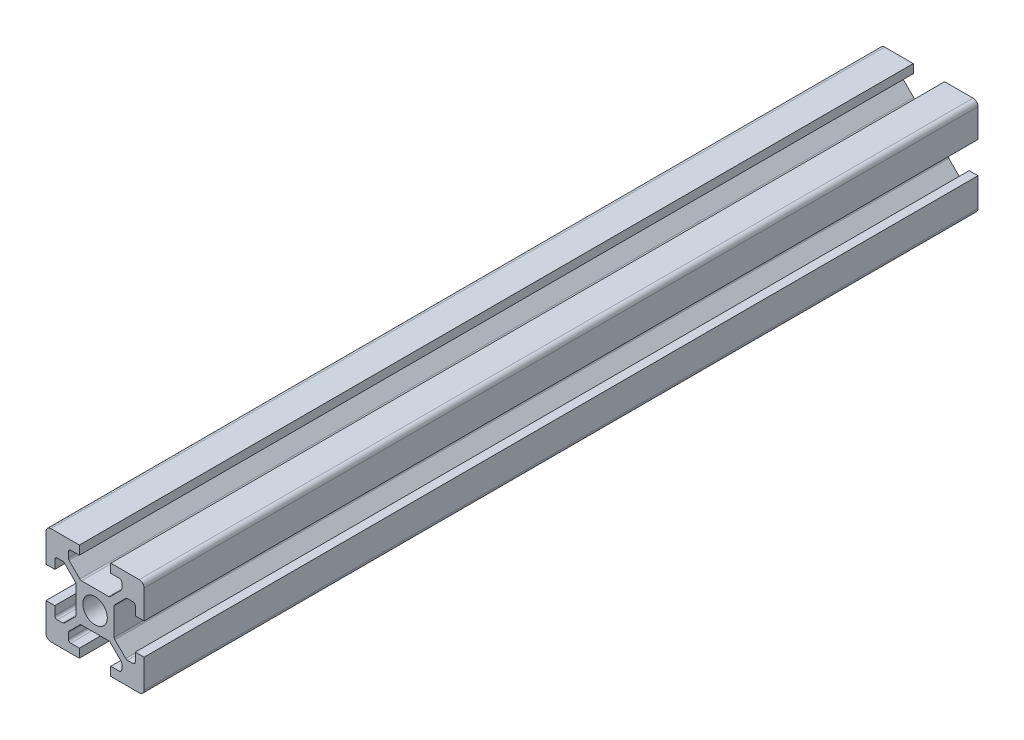
SolidWorks part; units mm, degrees
material "1060 Alloy"
ref_plane "Front Plane" through (0, 0, 0) normal (0, 0, 1) x (1, 0, 0)
ref_plane "Top Plane" through (0, 0, 0) normal (0, 1, 0) x (1, 0, 0)
ref_plane "Right Plane" through (0, 0, 0) normal (1, 0, 0) x (0, 0, -1)
sketch "Sketch1" plane through (0, 0, 0) normal (0, 0, 1) x (1, 0, 0)
  line L0 (20, 0) -> (-8.059, 28.059) construction
  line L1 (0, 0) -> (6.8, 0)
  line L2 (0, 0) -> (0, 6.8)
  line L3 (0, 20) -> (6.8, 20)
  line L4 (20, 0) -> (20, 6.8)
  line L5 (6.8, 20) -> (6.8, 18.2)
  line L6 (20, 20) -> (8.2322, 8.2322) construction
  line L7 (12.95, 6.1) -> (7.05, 6.1)
  line L8 (13.9, 7.05) -> (13.9, 12.95)
  line L9 (12.95, 13.9) -> (7.05, 13.9)
  line L10 (6.1, 7.05) -> (6.1, 12.95)
  line L11 (13.9, 6.1) -> (6.1, 13.9) construction
  line L12 (13.9, 13.9) -> (6.1, 6.1) construction
  line L13 (4.55, 16.4) -> (7.05, 13.9)
  line L14 (13.2, 18.2) -> (13.2, 20)
  line L15 (1.8, 6.8) -> (0, 6.8)
  line L16 (0, 13.2) -> (0, 20)
  line L17 (0, 13.2) -> (1.8, 13.2)
  line L18 (10, 10) -> (10, 13.9) construction
  line L19 (16.4, 4.55) -> (13.9, 7.05)
  line L20 (4.55, 16.4) -> (4.55, 18.2)
  line L21 (4.55, 18.2) -> (6.8, 18.2)
  line L22 (13.2, 18.2) -> (15.45, 18.2)
  line L23 (15.45, 18.2) -> (15.45, 16.4)
  line L24 (15.45, 16.4) -> (12.95, 13.9)
  line L25 (16.4, 4.55) -> (18.2, 4.55)
  line L26 (18.2, 4.55) -> (18.2, 6.8)
  line L27 (20, 6.8) -> (18.2, 6.8)
  line L28 (18.2, 13.2) -> (20, 13.2)
  line L29 (18.2, 13.2) -> (18.2, 15.45)
  line L30 (18.2, 15.45) -> (16.4, 15.45)
  line L31 (16.4, 15.45) -> (13.9, 12.95)
  line L32 (1.8, 4.55) -> (3.6, 4.55)
  line L33 (3.6, 15.45) -> (6.1, 12.95)
  line L34 (3.6, 15.45) -> (1.8, 15.45)
  line L35 (1.8, 15.45) -> (1.8, 13.2)
  line L36 (0, 13.2) -> (1.8, 13.2)
  line L37 (1.8, 6.8) -> (0, 6.8)
  line L38 (3.6, 4.55) -> (6.1, 7.05)
  line L39 (1.8, 6.8) -> (1.8, 4.55)
  line L40 (15.45, 3.6) -> (12.95, 6.1)
  line L41 (4.55, 3.6) -> (7.05, 6.1)
  line L42 (4.55, 1.8) -> (4.55, 3.6)
  line L43 (6.8, 1.8) -> (4.55, 1.8)
  line L44 (6.8, 1.8) -> (6.8, 0)
  line L45 (15.45, 3.6) -> (15.45, 1.8)
  line L46 (15.45, 1.8) -> (13.2, 1.8)
  line L47 (13.2, 0) -> (13.2, 1.8)
  line L48 (13.2, 20) -> (20, 20)
  line L49 (20, 13.2) -> (20, 20)
  line L50 (13.2, 0) -> (20, 0)
  line L51 (6.1, 6.1) -> (-5.5045, -5.5045) construction
  circle A0 centre (10, 10) radius 2.5
  point P25 (10, 16.4)
  point P39 (13.2, 19.1)
  point P46 (0.9, 6.8)
  dimension "D3" = 5
  dimension "D2" = 20
  dimension "D4" = 7.8
  dimension "D5" = 7.8
  dimension "D6" = 6.8
  dimension "D7" = 6.8
  dimension "D8" = 1.8
  dimension "D9" = 10.9
  dimension "D10" = 1.8
  dimension "D11" = 10.9
  dimension "D12" = 20
extrude "Boss-Extrude1" add sketch "Sketch1" along normal blind 170 contours L47 L50 L4 L27 L26 L25 L19 L8 L31 L30 L29 L28 L49 L48 L14 L22 L23 L24 L9 L13 L20 L21 L5 L3 L16 L17 L35 L34 L33 L10 L38 L32 L39 L15 L2 L1 L44 L43 L42 L41 L7 L40 L45 L46 A0 region at (0.2828, 3.4, 0)
fillet "Fillet1" radius 1 4 edges at (20, 20, 85) (20, 0, 85) (0, 0, 85) (0, 20, 85)
fillet "Fillet2" radius 0.5 6 edges at (4.55, 18.2, 85) (4.55, 16.4, 85) (7.05, 13.9, 85) (15.45, 18.2, 85) (15.45, 16.4, 85) (12.95, 13.9, 85)
fillet "Fillet3" radius 0.5 6 edges at (18.2, 15.45, 85) (16.4, 15.45, 85) (13.9, 12.95, 85) (18.2, 4.55, 85) (13.9, 7.05, 85) (16.4, 4.55, 85)
fillet "Fillet4" radius 0.5 6 edges at (1.8, 15.45, 85) (3.6, 15.45, 85) (6.1, 12.95, 85) (3.6, 4.55, 85) (1.8, 4.55, 85) (6.1, 7.05, 85)
fillet "Fillet5" radius 0.5 6 edges at (7.05, 6.1, 85) (4.55, 3.6, 85) (4.55, 1.8, 85) (15.45, 1.8, 85) (15.45, 3.6, 85) (12.95, 6.1, 85)
